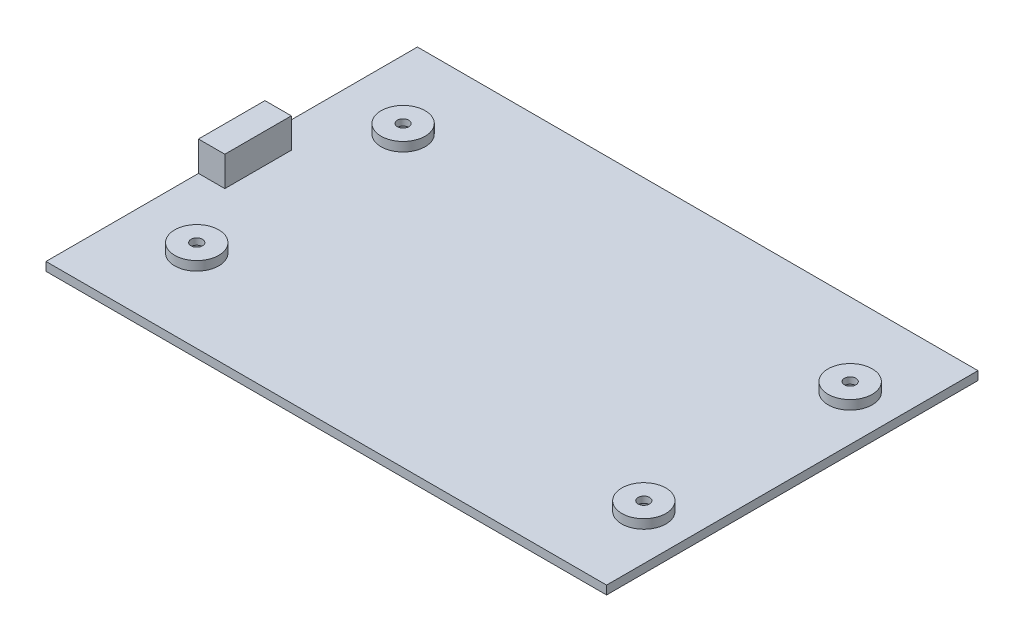
SolidWorks part; units mm, degrees
material "PLA"
ref_plane "前视基准面" through (0, 0, 0) normal (0, 0, 1) x (1, 0, 0)
ref_plane "上视基准面" through (0, 0, 0) normal (0, 1, 0) x (1, 0, 0)
ref_plane "右视基准面" through (0, 0, 0) normal (1, 0, 0) x (0, 0, -1)
other "Configuration Table"
sketch "草图1" plane through (0, 0, 0) normal (0, 1, 0) x (1, 0, 0)
  line L1 (-49.5144, 16.9583) -> (48.2856, 16.9583)
  line L2 (-49.5144, 16.9583) -> (-49.5144, -47.8417)
  line L3 (-49.5144, -47.8417) -> (48.2856, -47.8417)
  line L4 (48.2856, 16.9583) -> (48.2856, -47.8417)
  line L5 (-49.5144, 16.9583) -> (48.2856, -47.8417) construction
  line L6 (-49.5144, -47.8417) -> (48.2856, 16.9583) construction
  line L8 (-49.6144, -47.9417) -> (-49.6144, -20.4417) construction
  line L9 (48.3856, -47.9417) -> (-49.6144, -47.9417) construction
  point P0 (0, 0)
  dimension "D1" = 97.8
  dimension "D2" = 64.8
  dimension "D3" = 0.1
  dimension "D4" = 0.1
extrude "凸台-拉伸1" add sketch "草图1" along normal blind 1.5
sketch "草图2" plane through (0, 0, 0) normal (0, -1, 0) x (1, 0, 0)
  circle A0 centre (-37.6144, -2.5583) radius 6
  circle A1 centre (-37.6144, 33.4417) radius 6
  circle A2 centre (40.3856, -2.5583) radius 6
  circle A3 centre (40.3856, 33.4417) radius 6
  dimension "D1" = 12
  dimension "D2" = 12
  dimension "D3" = 12
  dimension "D4" = 12
extrude "切除-拉伸1" cut sketch "草图2" against normal blind 0.1
sketch "草图7" plane through (0, 1.5, 0) normal (0, 1, 0) x (1, 0, 0)
  line L1 (-44.6144, -15.4417) -> (47.3856, -15.4417) construction
  line L3 (-44.6144, 9.5583) -> (-44.6144, -40.4417) construction
  line L7 (47.3856, -40.4417) -> (47.3856, 9.5583) construction
  line L8 (1.3856, -15.4417) -> (1.3856, -40.4417) construction
  line L9 (-44.6144, -40.4417) -> (47.3856, -40.4417) construction
  circle A6 centre (-37.6144, 2.5583) radius 3.85
  circle A7 centre (-37.6144, 2.5583) radius 1
  circle A14 centre (-37.6144, -33.4417) radius 1
  circle A15 centre (-37.6144, -33.4417) radius 3.85
  circle A16 centre (40.3856, -33.4417) radius 3.85
  circle A17 centre (40.3856, -33.4417) radius 1
  circle A18 centre (40.3856, 2.5583) radius 1
  circle A19 centre (40.3856, 2.5583) radius 3.85
  dimension "D1" = 2
  dimension "D2" = 7.7
extrude "螺丝孔柱凸台-拉伸3" add sketch "草图7" along normal up to surface (1.6 mm away)
sketch "草图11" plane through (0, 0, 0) normal (0, -1, 0) x (1, 0, 0)
  line L0 (-56.3144, 9.6417) -> (-42.5144, 9.6417) construction
  line L1 (-44.9144, 9.6417) -> (-49.5144, 9.6417)
  line L2 (-44.9144, 9.6417) -> (-44.9144, 21.2417)
  line L3 (-44.9144, 21.2417) -> (-49.5144, 21.2417)
  line L4 (-49.5144, 9.6417) -> (-49.5144, 21.2417)
  line L5 (-42.5144, 21.2417) -> (-56.3144, 21.2417) construction
  line L6 (-49.6144, 19.9417) -> (-49.6144, 10.9417) construction
  dimension "D1" = 0.1
  dimension "D2" = 4.6
extrude "充电板档板凸台-拉伸5" add sketch "草图11" against normal up to surface (6.7 mm away)
sketch "草图12" plane through (0, 0, 0) normal (0, -1, 0) x (1, 0, 0)
  line L0 (-44.6144, 15.4417) -> (47.3856, 15.4417) construction
  line L1 (-44.6144, -9.5583) -> (-44.6144, 40.4417) construction
  line L2 (47.3856, 40.4417) -> (47.3856, -9.5583) construction
  line L3 (1.3856, 15.4417) -> (1.3856, -9.2596) construction
  circle A0 centre (-37.6144, -2.5583) radius 2.5
  circle A1 centre (-37.6144, 33.4417) radius 2.5
  circle A2 centre (40.3856, 33.4417) radius 2.5
  circle A3 centre (40.3856, -2.5583) radius 2.5
  dimension "D1" = 5
extrude "螺丝孔切除-拉伸2" cut sketch "草图12" against normal blind 2
sketch "草图13" plane through (-49.5144, 0, 0) normal (-1, 0, 0) x (0, 0, 1)
  line L0 (-16.9583, 0) -> (47.8417, 0) construction
  line L1 (11.1417, 2.5) -> (19.7417, 2.5)
  line L2 (11.1417, 2.5) -> (11.1417, 1)
  line L3 (11.1417, 1) -> (19.7417, 1)
  line L4 (19.7417, 2.5) -> (19.7417, 1)
  line L5 (15.4417, 6.7) -> (15.4417, 3.8504) construction
  line L6 (9.6417, 6.7) -> (21.2417, 6.7) construction
  line L7 (21.2417, 6.7) -> (21.2417, 1.5) construction
  dimension "D1" = 1.5
  dimension "D2" = 1
  dimension "D3" = 1.5
extrude "切除-拉伸2" cut sketch "草图13" against normal blind 1
